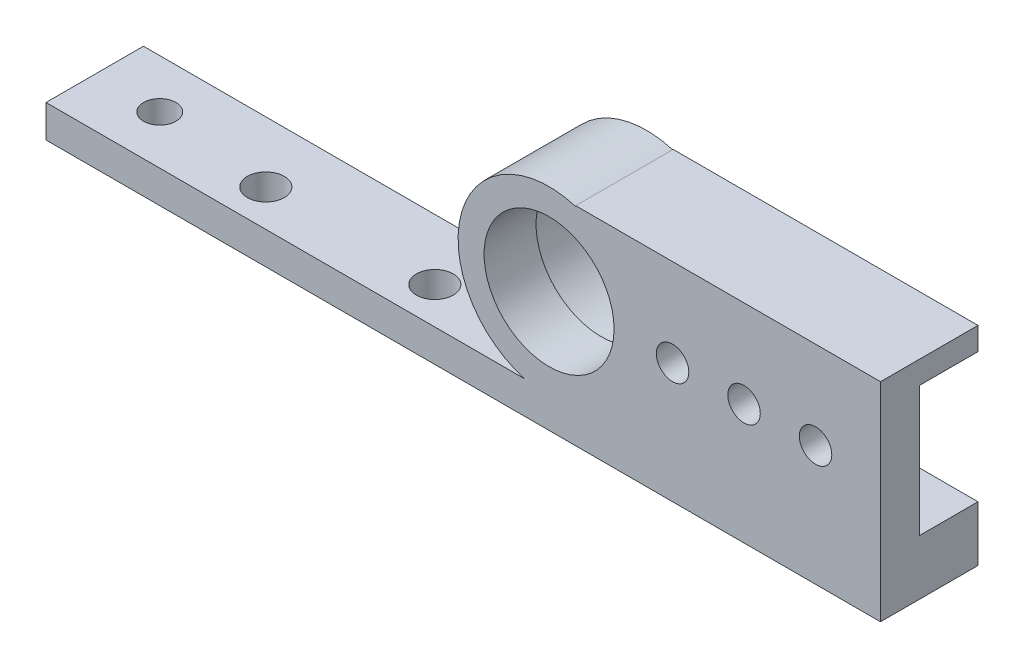
SolidWorks part; units mm, degrees
ref_plane "前视基准面" through (0, 0, 0) normal (0, 0, 1) x (1, 0, 0)
ref_plane "上视基准面" through (0, 0, 0) normal (0, 1, 0) x (1, 0, 0)
ref_plane "右视基准面" through (0, 0, 0) normal (1, 0, 0) x (0, 0, -1)
sketch "草图1" plane through (0, 0, 0) normal (0, 0, 1) x (1, 0, 0)
  line L1 (20, -10) -> (-20, -10)
  line L2 (20, -10) -> (20, 10)
  line L3 (20, 10) -> (-20, 10)
  line L4 (-20, -10) -> (-20, 10)
  line L5 (20, -10) -> (-20, 10) construction
  line L6 (20, 10) -> (-20, -10) construction
  point P0 (0, 0)
  dimension "D1" = 40
  dimension "D2" = 20
extrude "凸台-拉伸1" add sketch "草图1" along normal blind 6
sketch "草图2" plane through (0, 0, 6) normal (0, 0, 1) x (1, 0, 0)
  line L0 (20, -10) -> (20, 10) construction
  circle A0 centre (10, 0) radius 2.5
  circle A1 centre (-1, 0) radius 2.5
  circle A2 centre (-12, 0) radius 2.5
  dimension "D1" = 10
  dimension "D2" = 5
  dimension "D3" = 3
extrude "切除-拉伸1" cut sketch "草图2" against normal through all
sketch "草图3" plane through (0, 0, 6) normal (0, 0, 1) x (1, 0, 0)
  line L0 (20, 13.5) -> (20, 10)
  line L1 (20, -13.5) -> (-26.894, -13.5)
  line L3 (20, 13.5) -> (-26.894, 13.5)
  line L4 (-20, 10) -> (-20, -10)
  line L5 (-20, -10) -> (20, -10)
  line L6 (20, -10) -> (20, 10)
  line L7 (20, 10) -> (-20, 10)
  line L8 (-20, 10) -> (-20, -10)
  line L9 (-20, -10) -> (20, -10)
  line L10 (20, -10) -> (20, 10)
  line L11 (20, 10) -> (-20, 10)
  line L12 (-26.894, -13.5) -> (-26.894, 13.5)
  line L13 (20, -10.0394) -> (-26.894, 13.5) construction
  line L14 (20, 10.0394) -> (-26.894, -13.5) construction
  line L15 (20, -10) -> (20, -13.5)
  circle A0 centre (-31, 0) radius 11
  circle A1 centre (-31, 0) radius 14
  point P2 (0, 0)
  line M10 (-20, 10) -> (-20, -10)
  line M11 (-20, -10) -> (20, -10)
  line M13 (20, 10) -> (-20, 10)
  dimension "D3" = 22
  dimension "D4" = 28
  dimension "D2" = 3.5
  dimension "D1" = 0
extrude "凸台-拉伸2" add sketch "草图3" against normal blind 15 contours L3 A1 L1 L12 A0 | A1 L1 L15 M11 M10 | L1 A1 L8 A0 L12 | L8 A1 L3 L12 A0 | L8 A1 | A1 L0 L3 M10 M13 region at (-1.9449, 11.7771, 6) region at (-1.9449, -11.7771, 6) region at (-23.0173, 9.0328, 6) region at (-27.2274, 11.7946, 6) region at (-18.7882, 0, 6) region at (-23.0173, -9.0328, 6)
sketch "草图5" plane through (0, 0, 6) normal (0, 0, 1) x (1, 0, 0)
  circle A0 centre (-31, 0) radius 10
  circle A1 centre (-31, 0) radius 11 construction
  circle A2 centre (-31, 0) radius 11
  dimension "D1" = 20
extrude "凸台-拉伸3" add sketch "草图5" against normal blind 8
sketch "草图6" plane through (0, 0, 6) normal (0, 0, 1) x (1, 0, 0)
  circle A0 centre (-31, 0) radius 8.5
  circle A1 centre (-31, 0) radius 10 construction
  circle A2 centre (-31, 0) radius 10
  dimension "D1" = 17
sketch "草图9" plane through (0, -13.5, 0) normal (0, -1, 0) x (1, 0, 0)
  circle A0 centre (-18.2368, -1.344) radius 5.5352
sketch "草图10" plane through (20, 0, 0) normal (1, 0, 0) x (0, 0, -1)
  line L1 (9, -13.5) -> (-6, -13.5)
  line L2 (9, -13.5) -> (9, -18.5)
  line L3 (9, -18.5) -> (-6, -18.5)
  line L4 (-6, -13.5) -> (-6, -18.5)
  dimension "D1" = 5
extrude "凸台-拉伸4" add sketch "草图10" against normal blind 200
sketch "草图11" plane through (0, 0, 6) normal (0, 0, 1) x (1, 0, 0)
  line L1 (-28.6193, -11.8661) -> (-25.5243, -11.8661)
  line L2 (-28.6193, -11.8661) -> (-28.6193, -14.961)
  line L3 (-28.6193, -14.961) -> (-25.5243, -14.961)
  line L4 (-25.5243, -11.8661) -> (-25.5243, -14.961)
extrude "凸台-拉伸5" add sketch "草图11" against normal through all
sketch "草图13" plane through (0, -18.5, 0) normal (0, -1, 0) x (1, 0, 0)
  line L0 (-164.0842, 6) -> (-164.0842, -9)
  line L1 (-180, 6) -> (20, 6) construction
  line L2 (-164.0842, 123.2983) -> (-164.0842, -246.7017) construction
  line L3 (-180, -9) -> (20, -9) construction
sketch "草图14" plane through (0, -18.5, 0) normal (0, -1, 0) x (1, 0, 0)
  line L0 (-108.4077, -15.7251) -> (-108.4077, 9.3691)
  line L1 (-108.4077, 154.1686) -> (-108.4077, -215.8314) construction
sketch "草图15" plane through (0, -18.5, 0) normal (0, -1, 0) x (1, 0, 0)
  line L1 (-108.4077, -15.7251) -> (-184.1416, -15.7251)
  line L2 (-108.4077, -15.7251) -> (-108.4077, 11.9644)
  line L3 (-108.4077, 11.9644) -> (-184.1416, 11.9644)
  line L4 (-184.1416, -15.7251) -> (-184.1416, 11.9644)
sketch "草图16" plane through (0, -18.5, 0) normal (0, -1, 0) x (1, 0, 0)
  line L0 (-108.4077, -17.1171) -> (-108.4077, 37.1771)
  line L1 (-108.4077, 154.1686) -> (-108.4077, -215.8314) construction
sketch "草图17" plane through (0, -18.5, 0) normal (0, -1, 0) x (1, 0, 0)
  line L1 (-108.4077, -17.1171) -> (-191.9094, -17.1171)
  line L2 (-108.4077, -17.1171) -> (-108.4077, 25.2398)
  line L3 (-108.4077, 25.2398) -> (-191.9094, 25.2398)
  line L4 (-191.9094, -17.1171) -> (-191.9094, 25.2398)
extrude "切除-拉伸2" cut sketch "草图17" against normal through all
sketch "草图18" plane through (0, -18.5, 0) normal (0, -1, 0) x (1, 0, 0)
  line L0 (-108.4077, 6) -> (-108.4077, -9)
  line L1 (-108.4077, -1.5) -> (-98.4077, -1.5)
  circle A0 centre (-98.4077, -1.5) radius 2.5
  dimension "D2" = 5
  dimension "D1" = 10
extrude "切除-拉伸3" cut sketch "草图18" against normal blind 10 contours A0 region at (-98.4077, -18.5, -3.9293)
sketch "草图19" plane through (0, -18.5, 0) normal (0, -1, 0) x (1, 0, 0)
  circle A0 centre (-80.2361, 0.3438) radius 2.8371
  circle A1 centre (-54.2361, 0.3438) radius 2.8371
sketch "草图20" plane through (0, -18.5, 0) normal (0, -1, 0) x (1, 0, 0)
  circle A0 centre (-54.2361, 0.3438) radius 2.8371 construction
  circle A1 centre (-80.2361, 0.3438) radius 2.8371 construction
  circle A2 centre (-54.2361, 0.3438) radius 2.8371
  circle A3 centre (-80.2361, 0.3438) radius 2.8371
extrude "切除-拉伸4" cut sketch "草图20" against normal blind 10
